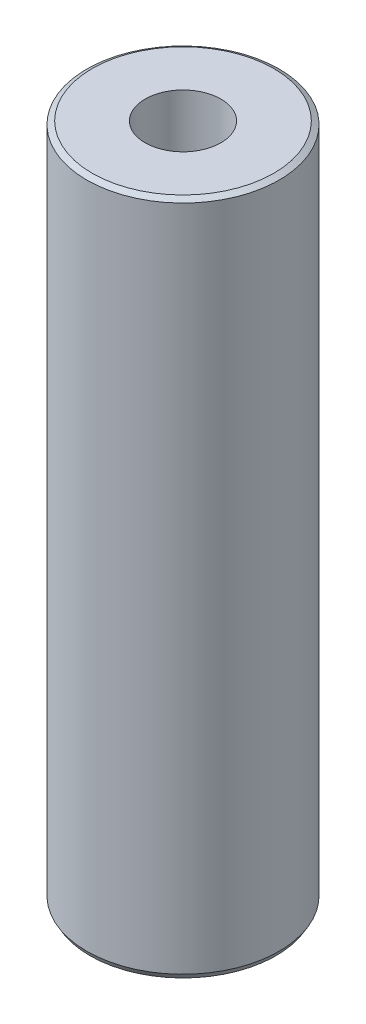
SolidWorks part; units mm, degrees
ref_plane "Front Plane" through (0, 0, 0) normal (0, 0, 1) x (1, 0, 0)
ref_plane "Top Plane" through (0, 0, 0) normal (0, 1, 0) x (1, 0, 0)
ref_plane "Right Plane" through (0, 0, 0) normal (1, 0, 0) x (0, 0, -1)
sketch "Sketch1" plane through (0, 0, 0) normal (0, 1, 0) x (1, 0, 0)
  circle A0 centre (0, 0) radius 37.5
  dimension "SHAFT_OD" = 75
extrude "Boss-Extrude1" add sketch "Sketch1" along normal blind 263.6698
sketch "Sketch2" plane through (0, 0, 0) normal (0, 1, 0) x (1, 0, 0)
  circle A0 centre (0, 0) radius 14.7807
  dimension "BORE_D" = 29.5615
extrude "Cut-Extrude1" cut sketch "Sketch2" along normal through all
chamfer "Chamfer1" distance 1.2245 angle 60 2 edges at (0, 263.6698, 37.5) (0, 0, 37.5) first distance on face at (0, 263.6698, 37.5) first distance on face at (0, 0, 14.7807)
